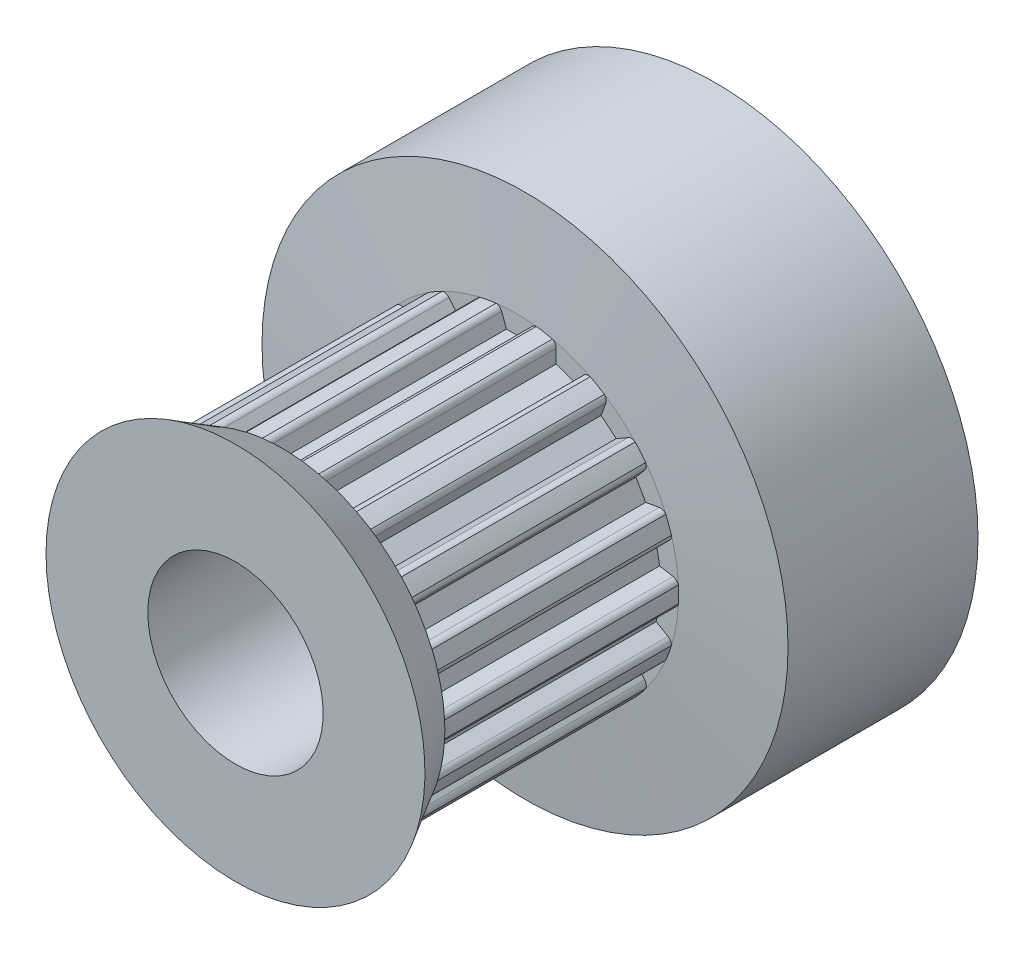
SolidWorks part; units mm, degrees
material "ABS"
ref_plane "Front Plane" through (0, 0, 0) normal (0, 0, 1) x (1, 0, 0)
ref_plane "Top Plane" through (0, 0, 0) normal (0, 1, 0) x (1, 0, 0)
ref_plane "Right Plane" through (0, 0, 0) normal (1, 0, 0) x (0, 0, -1)
sketch "Sketch8" plane through (0, 0, 0) normal (1, 0, 0) x (0, 0, -1)
  line L0 (7.5979, 0) -> (-14.162, 0) construction
  line L1 (10.8016, -3) -> (10.8016, -9)
  line L2 (4, -5.5563) -> (-4, -5.5563)
  line L3 (-5.606, -6.4835) -> (-4, -5.5563)
  line L4 (10.8016, -9) -> (4.3016, -9)
  line L5 (-5.606, -6.4835) -> (-5.606, -3)
  line L6 (4, -5.5563) -> (4.3016, -9)
  line L7 (0, 0) -> (0, -5.5563) construction
  line L13 (10.8016, -3) -> (-5.606, -3)
  dimension "D1" = 3
  dimension "D2" = 6.5
  dimension "D3" = 9
  dimension "D4" = 5.5563
  dimension "D5" = 30
  dimension "D6" = 8
revolve "Revolve1" add sketch "Sketch8" angle 360 about L0
sketch "Sketch7" plane through (0, 0, 0) normal (0, 0, 1) x (1, 0, 0)
  line L0 (-1.9984, 4.5111) -> (-1.3688, 4.7402)
  line L1 (-0.7423, 5.5127) -> (0.7423, 5.5127) construction
  line L4 (-1.3688, 4.7402) -> (-1.3688, 5.2095)
  line L5 (-1.9984, 4.5111) -> (-2.3, 4.8705)
  line L7 (-0.335, 4.9225) -> (0.335, 4.9225)
  line L9 (0.335, 4.9225) -> (0.4955, 5.3635)
  line L11 (-0.335, 4.9225) -> (-0.4955, 5.3635)
  line L12 (1.3688, 4.7402) -> (1.9984, 4.5111)
  line L13 (1.9984, 4.5111) -> (2.3, 4.8705)
  line L14 (1.3688, 4.7402) -> (1.3688, 5.2095)
  line L15 (2.9075, 3.9862) -> (3.4207, 3.5555)
  line L16 (3.4207, 3.5555) -> (3.8271, 3.7902)
  line L17 (2.9075, 3.9862) -> (3.068, 4.4272)
  line L18 (4.0955, 2.7514) -> (4.4305, 2.1711)
  line L19 (4.4305, 2.1711) -> (4.8926, 2.2526)
  line L20 (4.0955, 2.7514) -> (4.3971, 3.1108)
  line L21 (4.7895, 1.1847) -> (4.9059, 0.5249)
  line L22 (4.9059, 0.5249) -> (5.368, 0.4434)
  line L23 (4.7895, 1.1847) -> (5.1959, 1.4193)
  line L24 (4.9059, -0.5249) -> (4.7895, -1.1847)
  line L25 (4.7895, -1.1847) -> (5.1959, -1.4193)
  line L26 (4.9059, -0.5249) -> (5.368, -0.4434)
  line L27 (4.4305, -2.1711) -> (4.0955, -2.7514)
  line L28 (4.0955, -2.7514) -> (4.3971, -3.1108)
  line L29 (4.4305, -2.1711) -> (4.8926, -2.2526)
  line L30 (3.4207, -3.5555) -> (2.9075, -3.9862)
  line L31 (2.9075, -3.9862) -> (3.068, -4.4272)
  line L32 (3.4207, -3.5555) -> (3.8271, -3.7902)
  line L33 (1.9984, -4.5111) -> (1.3688, -4.7402)
  line L34 (1.3688, -4.7402) -> (1.3688, -5.2095)
  line L35 (1.9984, -4.5111) -> (2.3, -4.8705)
  line L36 (0.335, -4.9225) -> (-0.335, -4.9225)
  line L37 (-0.335, -4.9225) -> (-0.4955, -5.3635)
  line L38 (0.335, -4.9225) -> (0.4955, -5.3635)
  line L39 (-1.3688, -4.7402) -> (-1.9984, -4.5111)
  line L40 (-1.9984, -4.5111) -> (-2.3, -4.8705)
  line L41 (-1.3688, -4.7402) -> (-1.3688, -5.2095)
  line L42 (-2.9075, -3.9862) -> (-3.4207, -3.5555)
  line L43 (-3.4207, -3.5555) -> (-3.8271, -3.7902)
  line L44 (-2.9075, -3.9862) -> (-3.068, -4.4272)
  line L45 (-4.0955, -2.7514) -> (-4.4305, -2.1711)
  line L46 (-4.4305, -2.1711) -> (-4.8926, -2.2526)
  line L47 (-4.0955, -2.7514) -> (-4.3971, -3.1108)
  line L48 (-4.7895, -1.1847) -> (-4.9059, -0.5249)
  line L49 (-4.9059, -0.5249) -> (-5.368, -0.4434)
  line L50 (-4.7895, -1.1847) -> (-5.1959, -1.4193)
  line L51 (-4.9059, 0.5249) -> (-4.7895, 1.1847)
  line L52 (-4.7895, 1.1847) -> (-5.1959, 1.4193)
  line L53 (-4.9059, 0.5249) -> (-5.368, 0.4434)
  line L54 (-4.4305, 2.1711) -> (-4.0955, 2.7514)
  line L55 (-4.0955, 2.7514) -> (-4.3971, 3.1108)
  line L56 (-4.4305, 2.1711) -> (-4.8926, 2.2526)
  line L57 (-3.4207, 3.5555) -> (-2.9075, 3.9862)
  line L58 (-2.9075, 3.9862) -> (-3.068, 4.4272)
  line L59 (-3.4207, 3.5555) -> (-3.8271, 3.7902)
  arc A0 (0.7423, 5.5127) -> (0.4955, 5.3635) centre (0.7116, 5.2848) ccw
  arc A2 (-1.1879, 5.4342) -> (-1.3688, 5.2095) centre (-1.1388, 5.2095) ccw
  arc A3 (-2.3, 4.8705) -> (-2.583, 4.9264) centre (-2.4762, 4.7227) ccw
  arc A4 (-0.4955, 5.3635) -> (-0.7423, 5.5127) centre (-0.7116, 5.2848) ccw
  arc A6 (0.7423, 5.5127) -> (-0.7423, 5.5127) centre (0, 0) ccw
  arc A7 (2.583, 4.9264) -> (2.3, 4.8705) centre (2.4762, 4.7227) ccw
  arc A8 (-1.1879, 5.4342) -> (-2.583, 4.9264) centre (0, 0) ccw
  arc A9 (1.3688, 5.2095) -> (1.1879, 5.4342) centre (1.1388, 5.2095) ccw
  arc A10 (2.583, 4.9264) -> (1.1879, 5.4342) centre (0, 0) ccw
  arc A11 (4.1122, 3.7459) -> (3.8271, 3.7902) centre (3.9421, 3.591) ccw
  arc A12 (3.068, 4.4272) -> (2.9749, 4.7002) centre (2.8519, 4.5058) ccw
  arc A13 (4.1122, 3.7459) -> (2.9749, 4.7002) centre (0, 0) ccw
  arc A14 (5.1453, 2.1135) -> (4.8926, 2.2526) centre (4.9326, 2.0261) ccw
  arc A15 (4.3971, 3.1108) -> (4.403, 3.3992) centre (4.221, 3.2587) ccw
  arc A16 (5.1453, 2.1135) -> (4.403, 3.3992) centre (0, 0) ccw
  arc A17 (5.5579, 0.2262) -> (5.368, 0.4434) centre (5.3281, 0.2169) ccw
  arc A18 (5.1959, 1.4193) -> (5.3001, 1.6883) centre (5.0809, 1.6185) ccw
  arc A19 (5.5579, 0.2262) -> (5.3001, 1.6883) centre (0, 0) ccw
  arc A20 (5.3001, -1.6883) -> (5.1959, -1.4193) centre (5.0809, -1.6185) ccw
  arc A21 (5.368, -0.4434) -> (5.5579, -0.2262) centre (5.3281, -0.2169) ccw
  arc A22 (5.3001, -1.6883) -> (5.5579, -0.2262) centre (0, 0) ccw
  arc A23 (4.403, -3.3992) -> (4.3971, -3.1108) centre (4.221, -3.2587) ccw
  arc A24 (4.8926, -2.2526) -> (5.1453, -2.1135) centre (4.9326, -2.0261) ccw
  arc A25 (4.403, -3.3992) -> (5.1453, -2.1135) centre (0, 0) ccw
  arc A26 (2.9749, -4.7002) -> (3.068, -4.4272) centre (2.8519, -4.5058) ccw
  arc A27 (3.8271, -3.7902) -> (4.1122, -3.7459) centre (3.9421, -3.591) ccw
  arc A28 (2.9749, -4.7002) -> (4.1122, -3.7459) centre (0, 0) ccw
  arc A29 (1.1879, -5.4342) -> (1.3688, -5.2095) centre (1.1388, -5.2095) ccw
  arc A30 (2.3, -4.8705) -> (2.583, -4.9264) centre (2.4762, -4.7227) ccw
  arc A31 (1.1879, -5.4342) -> (2.583, -4.9264) centre (0, 0) ccw
  arc A32 (-0.7423, -5.5127) -> (-0.4955, -5.3635) centre (-0.7116, -5.2848) ccw
  arc A33 (0.4955, -5.3635) -> (0.7423, -5.5127) centre (0.7116, -5.2848) ccw
  arc A34 (-0.7423, -5.5127) -> (0.7423, -5.5127) centre (0, 0) ccw
  arc A35 (-2.583, -4.9264) -> (-2.3, -4.8705) centre (-2.4762, -4.7227) ccw
  arc A36 (-1.3688, -5.2095) -> (-1.1879, -5.4342) centre (-1.1388, -5.2095) ccw
  arc A37 (-2.583, -4.9264) -> (-1.1879, -5.4342) centre (0, 0) ccw
  arc A38 (-4.1122, -3.7459) -> (-3.8271, -3.7902) centre (-3.9421, -3.591) ccw
  arc A39 (-3.068, -4.4272) -> (-2.9749, -4.7002) centre (-2.8519, -4.5058) ccw
  arc A40 (-4.1122, -3.7459) -> (-2.9749, -4.7002) centre (0, 0) ccw
  arc A41 (-5.1453, -2.1135) -> (-4.8926, -2.2526) centre (-4.9326, -2.0261) ccw
  arc A42 (-4.3971, -3.1108) -> (-4.403, -3.3992) centre (-4.221, -3.2587) ccw
  arc A43 (-5.1453, -2.1135) -> (-4.403, -3.3992) centre (0, 0) ccw
  arc A44 (-5.5579, -0.2262) -> (-5.368, -0.4434) centre (-5.3281, -0.2169) ccw
  arc A45 (-5.1959, -1.4193) -> (-5.3001, -1.6883) centre (-5.0809, -1.6185) ccw
  arc A46 (-5.5579, -0.2262) -> (-5.3001, -1.6883) centre (0, 0) ccw
  arc A47 (-5.3001, 1.6883) -> (-5.1959, 1.4193) centre (-5.0809, 1.6185) ccw
  arc A48 (-5.368, 0.4434) -> (-5.5579, 0.2262) centre (-5.3281, 0.2169) ccw
  arc A49 (-5.3001, 1.6883) -> (-5.5579, 0.2262) centre (0, 0) ccw
  arc A50 (-4.403, 3.3992) -> (-4.3971, 3.1108) centre (-4.221, 3.2587) ccw
  arc A51 (-4.8926, 2.2526) -> (-5.1453, 2.1135) centre (-4.9326, 2.0261) ccw
  arc A52 (-4.403, 3.3992) -> (-5.1453, 2.1135) centre (0, 0) ccw
  arc A53 (-2.9749, 4.7002) -> (-3.068, 4.4272) centre (-2.8519, 4.5058) ccw
  arc A54 (-3.8271, 3.7902) -> (-4.1122, 3.7459) centre (-3.9421, 3.591) ccw
  arc A55 (-2.9749, 4.7002) -> (-4.1122, 3.7459) centre (0, 0) ccw
  point P152 (0, 0)
  dimension "D1" = 18
extrude "Cut-Extrude1" cut sketch "Sketch7" against normal blind 4 and the other way blind 4
sketch "Sketch9" plane through (0, 0, 0) normal (1, 0, 0) x (0, 0, -1)
  line L0 (0, 0) -> (15.7339, 0) construction
  line L1 (7.5516, 9) -> (7.5516, -9) construction
  line L2 (10.8016, -9) -> (10.8016, 9) construction
  line L3 (10.8016, 3) -> (5.8196, 3)
  line L4 (5.8196, 3) -> (4.0875, 0)
  line L5 (4.0875, 0) -> (5.8196, -3)
  line L6 (5.8196, -3) -> (10.8016, -3)
  line L7 (10.8016, 3) -> (10.8016, -3)
  line L8 (10.8016, 9) -> (4.3016, 9) construction
  line L9 (4.3016, -9) -> (10.8016, -9) construction
  line L11 (11.0157, 0) -> (9.2837, 3) [skipped]
  line L12 (9.2837, -3) -> (11.0157, 0) [skipped]
  circle A0 centre (7.5516, 0) radius 1.5
  circle A1 centre (7.5516, 0) radius 3 construction
  dimension "D1" = 3
  dimension "D2" = 6
extrude "Cut-Extrude2" cut sketch "Sketch9" against normal through all contours A0 region at (0, 0, -7.5516)
extrude "Cut-Extrude3" cut sketch "Sketch9<3>" against normal blind 6
sketch "Sketch9<3>" plane through (0, 0, 0) normal (1, 0, 0) x (0, 0, -1) same geometry as "Sketch9"
equation "\"rod_diameter\"= 8"
equation "\"rod_hole_thickness\"= 4"
equation "\"rod_radius\"= \"rod_diameter\" / 2"
equation "\"platter_diameter\"= 320"
equation "\"platter_radius\"= \"platter_diameter\" / 2"
equation "\"extruder_mount_hole_spacing\"= 75"
equation "\"arm_rod_spacing\"= 40"
equation "\"top_frame_spacing\"= 90"
equation "\"motor_level_rod_spacing\"= 15"
equation "\"linear_bearing_diameter\"= 15"
equation "\"z_rod_spacing\"= 75"
equation "\"platter_rod_spacing\"= 50"
equation "\"rod_nut_thickness\"= 6.5"
equation "\"rod_nut_inscribed_diameter\"= 13"
equation "\"z_height\"= 350"
equation "\"gear_pitch\"=2"
equation "\"r_gear_teeth\"= 450"
equation "\"theta_gear_teeth\"= 385"
equation "\"sheet_thickness\"=5"
equation "\"sheet_tab_hole_thickness\"= \"sheet_thickness\""
equation "\"sheet_tab_width\"= \"sheet_thickness\"*2"
equation "\"sheet_bolt_diameter\"= 3"
equation "\"sheet_bolt_length\"= 16"
equation "\"sheet_nut_diameter\"= 5.5"
equation "\"sheet_nut_thickness\"= 2.5"
equation "\"sheet_nut_depth\"= 10"
equation "\"bearing_outside_diameter\"= 22"
equation "\"bearing_thickness\"= 7"
equation "\"corner_part_thickness\"= \"sheet_thickness\" + \"bearing_thickness\""
equation "\"setscrew_nut_diameter\"= 6"
equation "\"setscrew_nut_thickness\"= 3"
equation "\"setscrew_bolt_diameter\"= 3"
equation "\"D1@Sketch9\"=\"setscrew_bolt_diameter\""
equation "\"D2@Sketch9\"=\"setscrew_nut_diameter\""
equation "\"motor_shaft_diameter\"= 6"
equation "\"D1@Sketch8\"=\"motor_shaft_diameter\"/2"
equation "\"D1@Cut-Extrude3\"= \"motor_shaft_diameter\" / 2 + \"setscrew_nut_thickness\""
